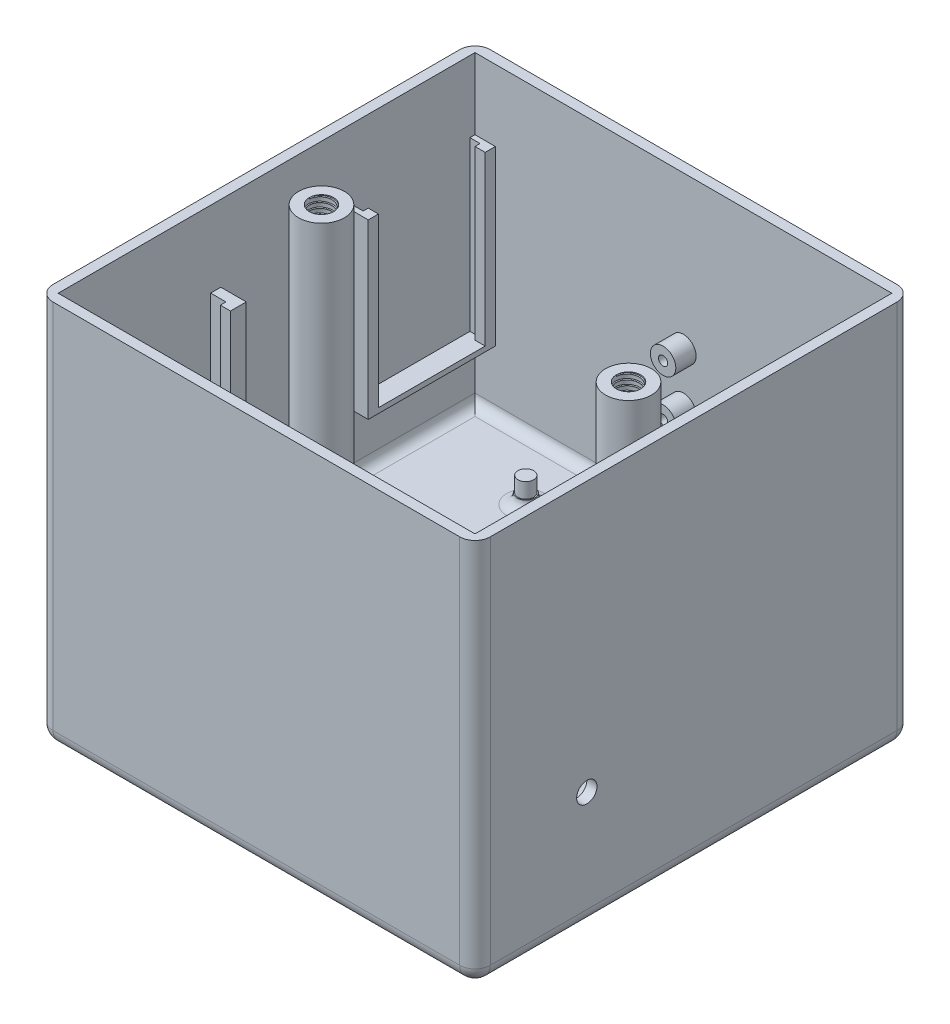
SolidWorks part; units mm, degrees
ref_plane "Front Plane" through (0, 0, 0) normal (0, 0, 1) x (1, 0, 0)
ref_plane "Top Plane" through (0, 0, 0) normal (0, 1, 0) x (1, 0, 0)
ref_plane "Right Plane" through (0, 0, 0) normal (1, 0, 0) x (0, 0, -1)
sketch "Sketch1" plane through (0, 0, 0) normal (0, 1, 0) x (1, 0, 0)
  line L1 (-43, 43) -> (43, 43)
  line L2 (-43, 43) -> (-43, -43)
  line L3 (-43, -43) -> (43, -43)
  line L4 (43, 43) -> (43, -43)
  line L5 (-43, 43) -> (43, -43) construction
  line L6 (-43, -43) -> (43, 43) construction
  point P0 (0, 0)
  dimension "D1" = 86
  dimension "D2" = 86
extrude "Boss-Extrude1" add sketch "Sketch1" along normal blind 76
sketch "Sketch2" plane through (0, 76, 0) normal (0, 1, 0) x (1, 0, 0)
  line L1 (-41, 41) -> (41, 41)
  line L2 (-41, 41) -> (-41, -41)
  line L3 (-41, -41) -> (41, -41)
  line L4 (41, 41) -> (41, -41)
  line L5 (-41, 41) -> (41, -41) construction
  line L6 (-41, -41) -> (41, 41) construction
  point P0 (0, 0)
  dimension "D1" = 82
  dimension "D2" = 82
extrude "Cut-Extrude1" cut sketch "Sketch2" against normal blind 60
sketch "Sketch3" plane through (0, 16, 0) normal (0, 1, 0) x (1, 0, 0)
  line L0 (-41, 41) -> (-41, -41) construction
  line L1 (-41, -41) -> (41, -41) construction
  line L2 (-19, 29) -> (-19, -29)
  line L3 (0, 41) -> (0, -41)
  line L4 (41, 41) -> (-41, 41) construction
  line L5 (-41, -41) -> (41, -41) construction
  circle A0 centre (-19, 29) radius 1.75
  circle A1 centre (-19, -29) radius 1.75
  circle A2 centre (19, -29) radius 1.75
  circle A3 centre (19, 29) radius 1.75
  dimension "D1" = 3.5
  dimension "D3" = 3.5
  dimension "D5" = 12
  dimension "D2" = 22
  dimension "D4" = 58
extrude "Boss-Extrude3" add sketch "Sketch3" along normal blind 2 contours A0 | A1 | A3 | A2
sketch "Sketch5" plane through (0, 18, 0) normal (0, 1, 0) x (1, 0, 0)
  line L0 (0, 0) -> (0, -12.2335)
  circle A0 centre (-19, 29) radius 1.55
  circle A1 centre (-19, -29) radius 1.55
  circle A2 centre (19, -29) radius 1.55
  circle A3 centre (19, 29) radius 1.55
  dimension "D1" = 3.1
  dimension "D2" = 3.1
extrude "Boss-Extrude4" add sketch "Sketch5" along normal blind 3 contours A0
ref_plane "Plane1" through (0, 0, 0) normal (1, 0, 0) x (0, 0, -1)
mirror "Mirror1" about plane through (0, 0, 0) normal (1, 0, 0) of "Boss-Extrude4"
ref_plane "Plane2" through (0, 0, 0) normal (0, 0, 1) x (1, 0, 0)
mirror "Mirror2" about plane through (0, 0, 0) normal (0, 0, 1) of "Mirror1", "Boss-Extrude4"
sketch "Sketch6" plane through (41, 0, 0) normal (-1, 0, 0) x (0, 0, 1)
  line L0 (41, 16) -> (-41, 16) construction
  line L2 (-41, 16) -> (-41, 76) construction
  circle A0 centre (-24.25, 56) radius 1.5
  circle A1 centre (24.25, 56) radius 1.5
  circle A2 centre (-24.25, 42.5) radius 1.5
  circle A3 centre (24.25, 42.5) radius 1.5
  circle A4 centre (-24.25, 49.25) radius 1.5
  circle A5 centre (24.25, 49.25) radius 1.5
  circle A6 centre (24.25, 35.75) radius 1.5
  circle A7 centre (-24.25, 35.75) radius 1.5
  dimension "D1" = 3
  dimension "D4" = 3
  dimension "D2" = 40
  dimension "D3" = 16.75
  dimension "D5" = 48.5
  dimension "D6" = 40
  dimension "D8" = 13.5
  dimension "D10" = 6.75
  dimension "D7" = 2
  dimension "D9" = 2
sketch "Sketch7" plane through (-41, 0, 0) normal (1, 0, 0) x (0, 0, -1)
  line L0 (41, 76) -> (-41, 76) construction
  line L1 (-41, 61.0234) -> (-9, 61.0234)
  line L2 (-41, 61.0234) -> (-41, 29.0234)
  line L3 (-41, 29.0234) -> (-9, 29.0234)
  line L4 (-9, 61.0234) -> (-9, 29.0234)
  line L5 (-41, 61.0234) -> (-9, 29.0234) construction
  line L6 (-41, 29.0234) -> (-9, 61.0234) construction
  line L7 (-41, 16) -> (-41, 76) construction
  point P0 (-25, 45.0234)
  dimension "D1" = 32
  dimension "D2" = 32
  dimension "D3" = 14.9766
  dimension "D4" = 0
extrude "Boss-Extrude6" add sketch "Sketch7" along normal blind 5
sketch "Sketch8" plane through (0, 61.0234, 0) normal (0, 1, 0) x (1, 0, 0)
  line L0 (-36, -9) -> (-41, -9) construction
  line L1 (-41, -11) -> (-38, -11)
  line L2 (-41, -11) -> (-41, -39)
  line L3 (-41, -39) -> (-38, -39)
  line L4 (-38, -11) -> (-38, -39)
  line L5 (-36, -41) -> (-41, -41) construction
  line L6 (-41, -9) -> (-41, -41) construction
  dimension "D1" = 2
  dimension "D2" = 2
  dimension "D3" = 0
  dimension "D4" = 3
extrude "Cut-Extrude2" cut sketch "Sketch8" against normal blind 30
sketch "Sketch9" plane through (0, 61.0234, 0) normal (0, 1, 0) x (1, 0, 0)
  line L0 (-36, -9) -> (-41, -9) construction
  line L1 (-38, -12.1) -> (-36, -12.1)
  line L2 (-38, -12.1) -> (-38, -38)
  line L3 (-38, -38) -> (-36, -38)
  line L4 (-36, -12.1) -> (-36, -38)
  line L6 (-41, -39) -> (-38, -39) construction
  line L7 (-38, -39) -> (-38, -11) construction
  line L8 (-36, -9) -> (-36, -41) construction
  dimension "D1" = 3.1
  dimension "D2" = 1
  dimension "D3" = 0
  dimension "D4" = 0
extrude "Cut-Extrude3" cut sketch "Sketch9" against normal blind 30
sketch "text label " plane through (-41, 0, 0) normal (1, 0, 0) x (0, 0, -1)
  text T0 "for the regulator\r\n"
sketch "text label  2" plane through (0, 16, 0) normal (0, 1, 0) x (1, 0, 0)
  text T0 "main pcb"
sketch "Sketch13" plane through (-41, 0, 0) normal (1, 0, 0) x (0, 0, -1)
  line L0 (41, 16) -> (41, 76) construction
  line L1 (16, 62) -> (41, 62)
  line L2 (16, 62) -> (16, 28)
  line L3 (16, 28) -> (41, 28)
  line L4 (41, 62) -> (41, 28)
  line L5 (41, 16) -> (-41, 16) construction
  dimension "D1" = 0
  dimension "D2" = 25
  dimension "D3" = 34
  dimension "D4" = 12
extrude "Boss-Extrude7" add sketch "Sketch13" along normal blind 4
sketch "Sketch14" plane through (0, 62, 0) normal (0, 1, 0) x (1, 0, 0)
  line L1 (-41, 40) -> (-39, 40)
  line L2 (-41, 40) -> (-41, 17)
  line L3 (-41, 17) -> (-39, 17)
  line L4 (-39, 40) -> (-39, 17)
  line L5 (41, 41) -> (-41, 41) construction
  line L6 (-37, 16) -> (-41, 16) construction
  line L7 (-41, 41) -> (-41, 16) construction
  dimension "D1" = 1
  dimension "D2" = 1
  dimension "D3" = 2
  dimension "D4" = 0
extrude "Cut-Extrude4" cut sketch "Sketch14" against normal blind 33
sketch "Sketch15" plane through (0, 62, 0) normal (0, 1, 0) x (1, 0, 0)
  line L0 (-39, 17) -> (-39, 40) construction
  line L1 (-39, 39) -> (-37, 39)
  line L2 (-39, 39) -> (-39, 18)
  line L3 (-39, 18) -> (-37, 18)
  line L4 (-37, 39) -> (-37, 18)
  line L5 (-37, 41) -> (-37, 16) construction
  line L6 (-39, 40) -> (-41, 40) construction
  line L7 (-41, 17) -> (-39, 17) construction
  dimension "D1" = 0
  dimension "D2" = 0
  dimension "D3" = 1
  dimension "D4" = 1
extrude "Cut-Extrude5" cut sketch "Sketch15" against normal blind 33
sketch "Sketch23" plane through (0, 0, -41) normal (0, 0, 1) x (1, 0, 0)
  line L0 (-41, 62) -> (-41, 76) construction
  line L1 (41, 16) -> (-41, 16) construction
  circle A0 centre (0, 46) radius 2.5
  dimension "D1" = 5
  dimension "D2" = 41
  dimension "D3" = 30
extrude "Boss-Extrude8" add sketch "Sketch23" along normal blind 4
sketch "Sketch24" plane through (0, 0, -37) normal (0, 0, 1) x (1, 0, 0)
  circle A0 centre (0, 46) radius 0.9
  dimension "D1" = 1.8
extrude "Cut-Extrude7" cut sketch "Sketch24" against normal blind 3
pattern_linear "LPattern1" count 2 spacing 10 along (0, -1, 0) of "Boss-Extrude8", "Cut-Extrude7"
sketch "Sketch25" plane through (0, 0, -41) normal (0, 0, 1) x (1, 0, 0)
  text T0 "battery holder"
sketch "Sketch26" plane through (0, 16, 0) normal (0, 1, 0) x (1, 0, 0)
  line L1 (-41, -41) -> (41, -41) construction
  circle A0 centre (-30.2, 0) radius 4.5
  dimension "D2" = 9
  dimension "D1" = 30.2
  dimension "D3" = 41
extrude "Boss-Extrude9" add sketch "Sketch26" along normal blind 60
sketch "Sketch27" plane through (0, 76, 0) normal (0, 1, 0) x (1, 0, 0)
  circle A0 centre (-30.2, 0) radius 2.4
  dimension "D1" = 4.8
extrude "Cut-Extrude8" cut sketch "Sketch27" against normal blind 40
ref_plane "Plane4" through (0, 0, 0) normal (1, 0, 0) x (0, 0, -1)
mirror "Mirror3" about plane through (0, 0, 0) normal (1, 0, 0) of "Cut-Extrude8", "Boss-Extrude9"
sketch "Sketch28" plane through (0, 0, 41) normal (0, 0, -1) x (-1, 0, 0)
  line L0 (-41, 16) -> (-41, 76) construction
  line L1 (41, 16) -> (-41, 16) construction
  circle A0 centre (-24.25, 56) radius 1.5
  circle A1 centre (24.25, 56) radius 1.5
  circle A2 centre (-24.25, 42.5) radius 1.5
  circle A3 centre (24.25, 42.5) radius 1.5
  dimension "D1" = 3
  dimension "D3" = 3
  dimension "D7" = 3
  dimension "D10" = 3
  dimension "D2" = 16.75
  dimension "D4" = 48.5
  dimension "D5" = 40
  dimension "D6" = 40
  dimension "D8" = 13.5
  dimension "D9" = 16.75
  dimension "D11" = 48.5
  dimension "D12" = 13.5
extrude "Boss-Extrude10" add sketch "Sketch28" along normal blind 5
sketch "Sketch29" plane through (0, 0, 36) normal (0, 0, -1) x (-1, 0, 0)
  circle A0 centre (-24.25, 56) radius 0.6
  circle A1 centre (-24.25, 42.5) radius 0.6
  circle A2 centre (24.25, 56) radius 0.6
  circle A3 centre (24.25, 42.5) radius 0.6
  dimension "D1" = 1.2
  dimension "D2" = 1.2
  dimension "D3" = 1.2
  dimension "D4" = 1.2
extrude "Cut-Extrude9" cut sketch "Sketch29" against normal blind 3
pattern_linear "LPattern2" count 2 spacing 6.75 along (0, -1, 0) of "Boss-Extrude10", "Cut-Extrude9"
sketch "text label 4" plane through (0, 0, 41) normal (0, 0, -1) x (-1, 0, 0)
  text T0 "for the relay\r\n"
fillet "Fillet2" radius 2 10 edges at (0, 16, 41) (-41, 16, 0) (0, 16, -41) (41, 16, 0) (-19, 16, -27.25) (-19, 16, 30.75) (19, 16, -27.25) (19, 16, 30.75) (-30.2, 16, 4.5) (30.2, 16, 4.5)
sketch "Sketch34" plane through (41, 0, 0) normal (-1, 0, 0) x (0, 0, 1)
  line L0 (-41, 18) -> (41, 18) construction
  line L1 (41, 18) -> (41, 76) construction
  circle A0 centre (21, 23) radius 2
  dimension "D1" = 4
  dimension "D2" = 5
  dimension "D3" = 20
extrude "Cut-Extrude10" cut sketch "Sketch34" against normal through all
sketch "text label 5" plane through (41, 0, 0) normal (-1, 0, 0) x (0, 0, 1)
  text T0 "power in"
thread "Thread1" pitch 0.3175 method extrude profile "Thread Profile2" start angle 0, offset 0, length 20, pitch 1, diameter 4.8
ref_plane "Plane6" through (27.8, 76, 0) normal (0, 0, 1) x (-1, 0, 0)
sketch "Thread Profile2" plane through (27.8, 76, 0) normal (0, 0, 1) x (-1, 0, 0)
  line L0 (0, 0) -> (0, 0.3175) construction
  line L11 (0, 0) -> (0, 0.2778)
  line L12 (0, 0.2778) -> (-0.1719, 0.1786)
  line L13 (-0.1719, 0.1786) -> (-0.1719, 0.0992)
  line L15 (-0.1719, 0.0992) -> (0, 0)
  line L17 (-0.1719, 0.1389) -> (0, 0.1389) construction
  point P2 (0, 0)
  dimension "Pitch" = 0.3175
  dimension "Profile_Angle" = 60
  dimension "Profile_Land" = 0.0794
  dimension "Profile_Height" = 0.1719
thread "Thread2" pitch 0.3175 method extrude profile "Thread Profile3" start angle 0, offset 0, length 20, pitch 1, diameter 4.8
ref_plane "Plane7" through (-32.6, 76, 0) normal (0, 0, 1) x (-1, 0, 0)
sketch "Thread Profile3" plane through (-32.6, 76, 0) normal (0, 0, 1) x (-1, 0, 0)
  line L0 (0, 0) -> (0, 0.3175) construction
  line L11 (0, 0) -> (0, 0.2778)
  line L12 (0, 0.2778) -> (-0.1719, 0.1786)
  line L13 (-0.1719, 0.1786) -> (-0.1719, 0.0992)
  line L15 (-0.1719, 0.0992) -> (0, 0)
  line L17 (-0.1719, 0.1389) -> (0, 0.1389) construction
  point P2 (0, 0)
  dimension "Pitch" = 0.3175
  dimension "Profile_Angle" = 60
  dimension "Profile_Land" = 0.0794
  dimension "Profile_Height" = 0.1719
fillet "Fillet3" radius 3 8 edges at (43, 0, 0) (43, 38, -43) (0, 0, -43) (-43, 38, -43) (-43, 0, 0) (-43, 38, 43) (43, 38, 43) (0, 0, 43)
